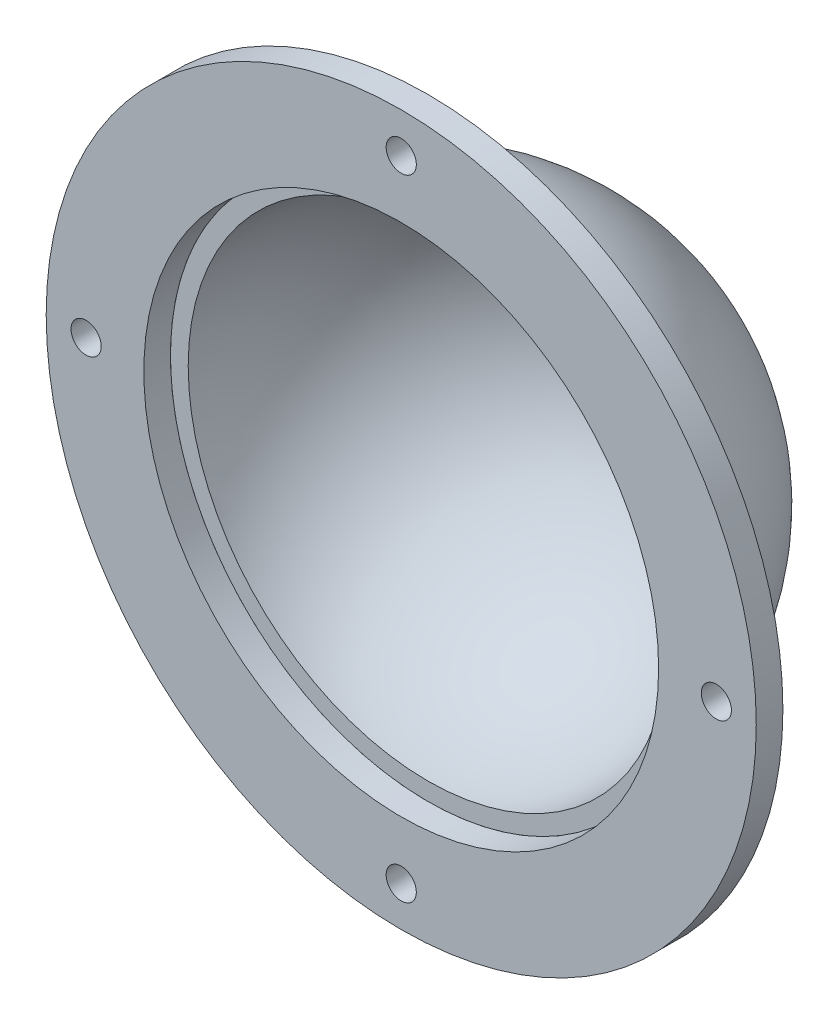
SolidWorks part; units mm, degrees
material "ABS"
ref_plane "前视基准面" through (0, 0, 0) normal (0, 0, 1) x (1, 0, 0)
ref_plane "上视基准面" through (0, 0, 0) normal (0, 1, 0) x (1, 0, 0)
ref_plane "右视基准面" through (0, 0, 0) normal (1, 0, 0) x (0, 0, -1)
sketch "草图1" plane through (0, 0, 0) normal (0, 0, 1) x (1, 0, 0)
  line L0 (0, 35.5) -> (0, 0) construction
  line L1 (0, 0) -> (35.5, 0) construction
  circle A0 centre (0, 0) radius 40
  circle A1 centre (0, 0) radius 35.5 construction
  circle A2 centre (0, 35.5) radius 1.7
  circle A3 centre (35.5, 0) radius 1.7
  circle A4 centre (0, -35.5) radius 1.7
  circle A5 centre (-35.5, 0) radius 1.7
  circle A6 centre (0, 0) radius 29
  point P16 (0, 0)
  dimension "D1" = 80
  dimension "D3" = 3.4
  dimension "D5" = 90
  dimension "D2" = 4.5
  dimension "D6" = 6.5
  dimension "D4" = 4
extrude "凸台-拉伸1" add sketch "草图1" along normal blind 3
sketch "草图2" plane through (0, 0, 0) normal (0, 1, 0) x (1, 0, 0)
  line L1 (29, 0) -> (-29, 0) construction
  line L2 (29, 0) -> (-29, 0)
  line L3 (0, 29) -> (0, 0.504)
  arc A0 (0, 29) -> (29, 0) centre (0, 0) cw
  arc A1 (0, 27) -> (27, 0) centre (0, 0) cw
  dimension "D1" = 2
revolve "旋转1" add sketch "草图2" angle 360 about L3 region at (28, 0, -0.4101)
